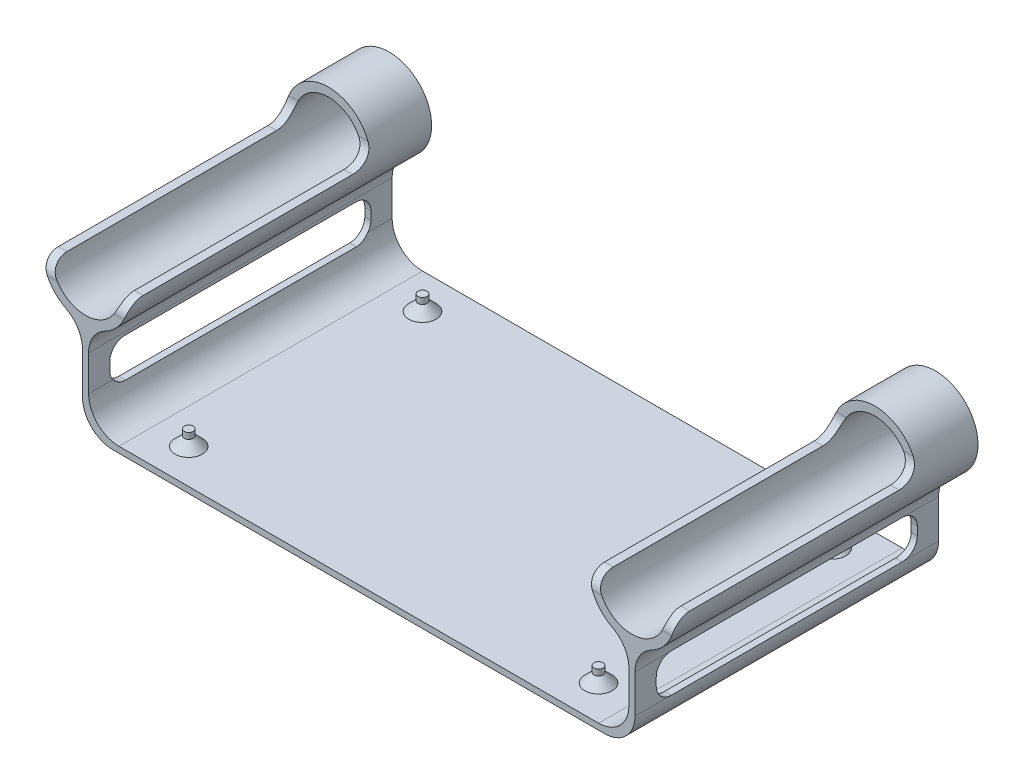
SolidWorks part; units mm, degrees
ref_plane "Front Plane" through (0, 0, 0) normal (0, 0, 1) x (1, 0, 0)
ref_plane "Top Plane" through (0, 0, 0) normal (0, 1, 0) x (1, 0, 0)
ref_plane "Right Plane" through (0, 0, 0) normal (1, 0, 0) x (0, 0, -1)
sketch "Sketch1" plane through (0, 0, 0) normal (0, 0, 1) x (1, 0, 0)
  line L0 (180, -14.9972) -> (180, -45) construction
  line L1 (0, -14) -> (0, -45) construction
  line L2 (180, -45) -> (181, -45)
  line L3 (181, -45) -> (181, -14.9615)
  line L4 (179, -43) -> (179, -14.9615)
  line L5 (0, -45) -> (-1, -45)
  line L6 (-1, -45) -> (-1, -13.9642)
  line L7 (179, -43) -> (1, -43)
  line L8 (1, -43) -> (1, -13.9642)
  line L14 (180, -45) -> (0, -45)
  circle A0 centre (0, 0) radius 11.15
  circle A1 centre (180, -0.9972) radius 11.15
  arc A2 (0, 14) -> (-1, -13.9642) centre (0, 0) ccw
  arc A3 (181, -14.9615) -> (180, 13.0028) centre (180, -0.9972) ccw
  arc A4 (180, 13.0028) -> (179, -14.9615) centre (180, -0.9972) ccw
  arc A5 (0, 14) -> (1, -13.9642) centre (0, 0) cw
  dimension "D1" = 22.3
  dimension "D2" = 22.3
  dimension "D4" = 28
  dimension "D9" = 180
  dimension "D3" = 2
  dimension "D5" = 2
  dimension "D6" = 1
  dimension "D7" = 1
  dimension "D8" = 1
  dimension "D10" = 45
extrude "Boss-Extrude1" add sketch "Sketch1" along normal blind 100
fillet "Fillet1" radius 10 8 edges at (181, -14.9615, 50) (179, -14.9615, 50) (1, -13.9642, 50) (-1, -13.9642, 50) (-1, -45, 50) (1, -43, 50) (179, -43, 50) (181, -45, 50)
sketch "Sketch2" plane through (0, -43, 0) normal (0, 1, 0) x (1, 0, 0)
  line L0 (90, -100) -> (90, 0) construction
  line L1 (169, -100) -> (11, -100) construction
  line L2 (169, 0) -> (11, 0) construction
  line L3 (157.5, -88.5) -> (90, -88.5) construction
  circle A0 centre (157.5, -88.5) radius 1.5
  circle A1 centre (22.5, -88.5) radius 1.5
  circle A2 centre (22.5, -11.5) radius 1.5
  circle A3 centre (157.5, -11.5) radius 1.5
  dimension "D1" = 3
  dimension "D2" = 67.5
  dimension "D5" = 11.5
  dimension "D3" = 2
  dimension "D4" = 2
extrude "Boss-Extrude2" add sketch "Sketch2" along normal blind 5
sketch "Sketch3" plane through (181, 0, 0) normal (1, 0, 0) x (0, 0, -1)
  line L0 (-100, -35) -> (0, -35) construction
  line L1 (-88, -35) -> (-12, -35)
  line L2 (-93, -30) -> (-93, -27.3279)
  line L3 (-88, -22.3279) -> (-12, -22.3279)
  line L4 (-7, -30) -> (-7, -27.3279)
  line L5 (0, -22.3279) -> (-100, -22.3279) construction
  line L6 (-100, -35) -> (-100, -22.3279) construction
  line L7 (0, -35) -> (0, -22.3279) construction
  arc A0 (-12, -35) -> (-7, -30) centre (-12, -30) ccw
  arc A1 (-12, -22.3279) -> (-7, -27.3279) centre (-12, -27.3279) cw
  arc A2 (-93, -27.3279) -> (-88, -22.3279) centre (-88, -27.3279) cw
  arc A3 (-88, -35) -> (-93, -30) centre (-88, -30) cw
  point P16 (-7, -22.3279)
  point P21 (-93, -35)
  dimension "D3" = 5
  dimension "D1" = 7
  dimension "D2" = 7
extrude "Cut-Extrude1" cut sketch "Sketch3" against normal blind 200
chamfer "Chamfer1" distance 3 angle 45 4 edges at (24, -43, 88.5) (24, -43, 11.5) (159, -43, 11.5) (159, -43, 88.5)
sketch "Sketch4" plane through (0, 0, 100) normal (0, 0, 1) x (1, 0, 0)
  line L1 (207.0653, -1) -> (-41.6581, -1)
  line L2 (207.0653, -1) -> (207.0653, 66.4454)
  line L3 (207.0653, 66.4454) -> (-41.6581, 66.4454)
  line L4 (-41.6581, -1) -> (-41.6581, 66.4454)
  circle A0 centre (0, 0) radius 11.15 construction
  dimension "D2" = 1
  dimension "D1" = 248.7234
extrude "Cut-Extrude2" cut sketch "Sketch4" against normal blind 80
fillet "Fillet2" radius 6 4 edges at (167.425, -1, 20) (192.575, -1, 20) (-12.5347, -1, 20) (12.5347, -1, 20)
fillet "Fillet4" radius 5 4 edges at (-12.5347, -1, 100) (12.5347, -1, 100) (167.425, -1, 100) (192.575, -1, 100)
